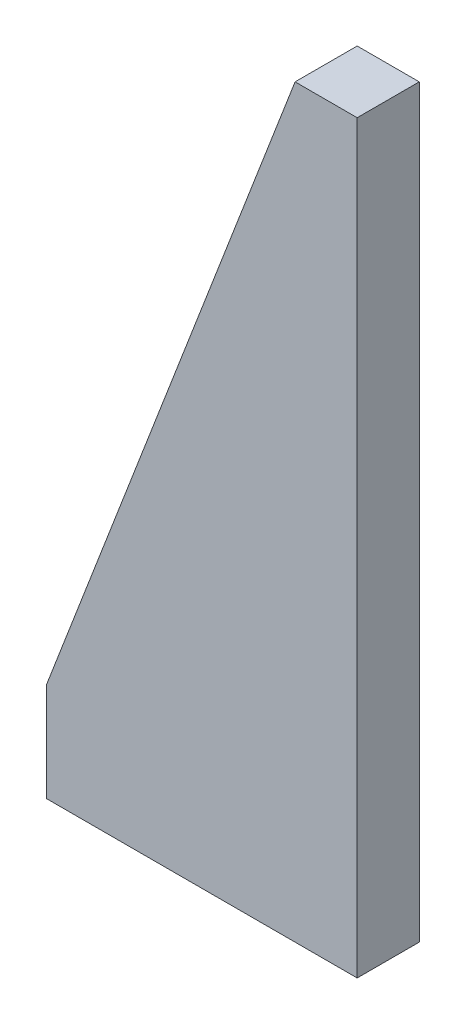
SolidWorks part; units mm, degrees
ref_plane "Спереди" through (0, 0, 0) normal (0, 0, 1) x (1, 0, 0)
ref_plane "Сверху" through (0, 0, 0) normal (0, 1, 0) x (1, 0, 0)
ref_plane "Справа" through (0, 0, 0) normal (1, 0, 0) x (0, 0, -1)
sketch "Эскиз1" plane through (0, 0, 0) normal (0, 0, 1) x (1, 0, 0)
  line L0 (0, 300) -> (-25, 300)
  line L1 (-25, 300) -> (-125, 40)
  line L2 (-125, 40) -> (-125, 0)
  line L3 (-125, 0) -> (0, 0)
  line L4 (0, 0) -> (0, 300)
extrude "Бобышка-Вытянуть1" add sketch "Эскиз1" along normal mid plane 25
